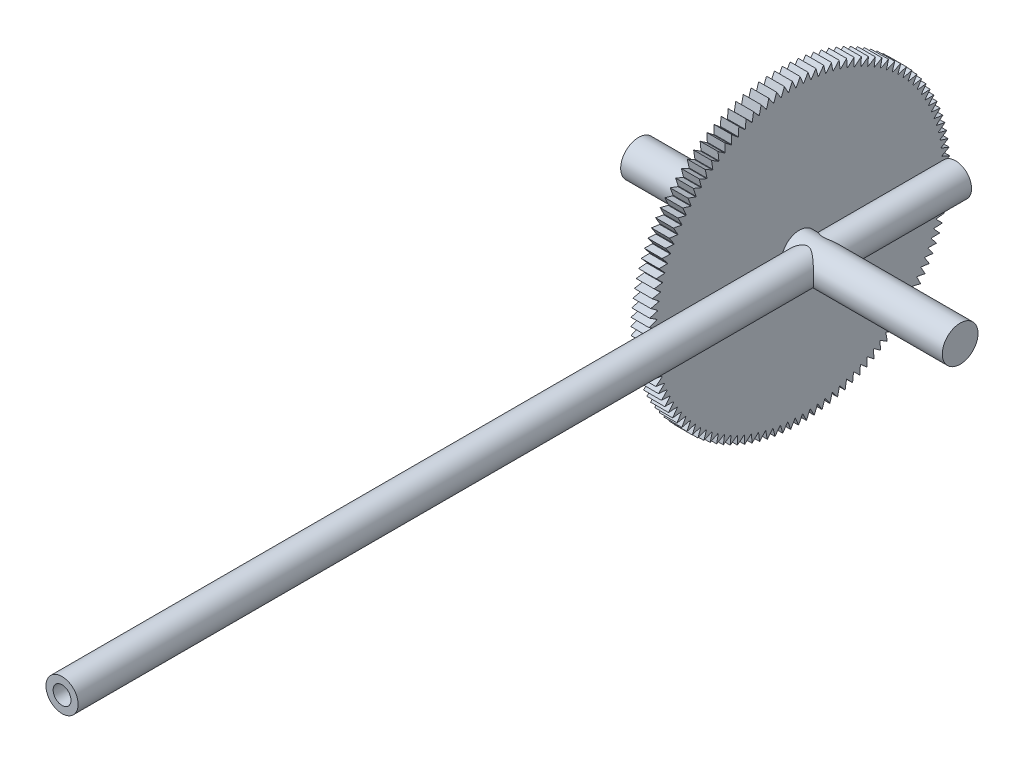
SolidWorks part; units mm, degrees
ref_plane "前视基准面" through (0, 0, 0) normal (0, 0, 1) x (1, 0, 0)
ref_plane "上视基准面" through (0, 0, 0) normal (0, 1, 0) x (1, 0, 0)
ref_plane "右视基准面" through (0, 0, 0) normal (1, 0, 0) x (0, 0, -1)
other "Configuration Table"
sketch "草图1" plane through (0, 0, 0) normal (0, 0, 1) x (1, 0, 0)
  circle A0 centre (0, 0) radius 2.5
  circle A1 centre (0, 0) radius 4.5
  dimension "D1" = 5
  dimension "D2" = 2
extrude "凸台-拉伸1" add sketch "草图1" along normal blind 200 and the other way blind 50
ref_plane "基准面1" through (-4.5, 0, 0) normal (-1, 0, 0) x (0, 0, 1)
sketch "草图3" plane through (-4.5, 0, 0) normal (-1, 0, 0) x (0, 0, 1)
  circle A0 centre (-10.8092, 0) radius 5
  dimension "D1" = 10
extrude "凸台-拉伸2" add sketch "草图3" along normal blind 45 and the other way blind 45 separate body contours A0
sketch "草图4" plane through (0, 0, -50) normal (0, 0, -1) x (-1, 0, 0)
  circle A0 centre (0, 0) radius 2.5 construction
  circle A1 centre (0, 0) radius 2.5
extrude "切除-拉伸1" cut sketch "草图4" against normal through all
sketch "草图5" plane through (-4.5, 0, 0) normal (-1, 0, 0) x (0, 0, 1)
  circle A2 centre (-10.8092, 0) radius 40
extrude "凸台-拉伸6" add sketch "草图5" along normal blind 5 separate body
sketch "草图6" plane through (-9.5, 0, 0) normal (-1, 0, 0) x (0, 0, 1)
  line L1 (-7.8411, 39.8897) -> (-8.8258, 42.0919)
  line L2 (-8.8258, 42.0919) -> (-9.8105, 39.9875)
  circle A1 centre (-10.8092, 0) radius 40
  arc A2 (-7.8411, 39.8897) -> (-9.8105, 39.9875) centre (-10.8092, 0) ccw
  dimension "D1" = 0
extrude "凸台-拉伸7" add sketch "草图6" against normal up to surface (5 mm away) up to face at (-4.5, 0, 29.1908)
pattern_circular "阵列(圆周)1" count 120 every 3 about axis through (-9.5, 0, -10.8092) along (-1, 0, 0) of "凸台-拉伸7"
sketch "草图7" plane through (-49.5, 0, 0) normal (-1, 0, 0) x (0, 0, 1)
  circle A1 centre (-10.8092, 0) radius 5
  circle A2 centre (-10.8092, 0) radius 5
  point P1 (-10.8092, 0)
  dimension "D1" = 0
